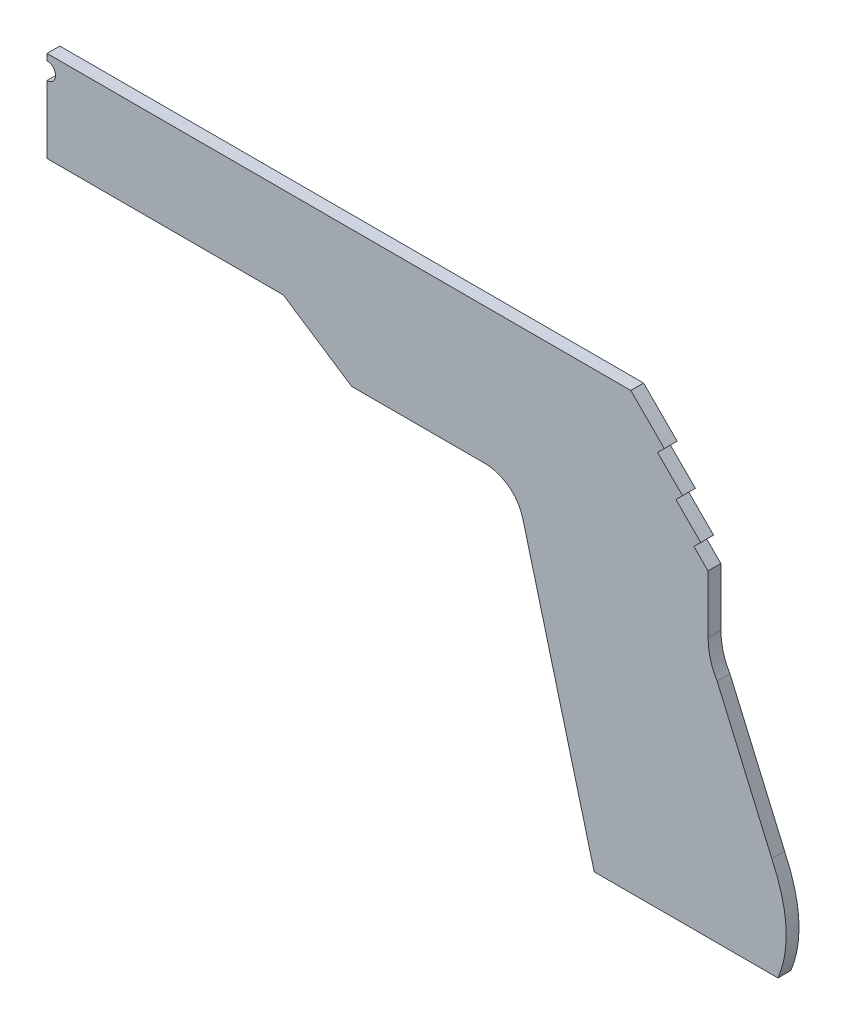
SolidWorks part; units mm, degrees
ref_plane "Front Plane" through (0, 0, 0) normal (0, 0, 1) x (1, 0, 0)
ref_plane "Top Plane" through (0, 0, 0) normal (0, 1, 0) x (1, 0, 0)
ref_plane "Right Plane" through (0, 0, 0) normal (1, 0, 0) x (0, 0, -1)
sketch "Sketch1" plane through (0, 0, 0) normal (0, 0, 1) x (1, 0, 0)
  line L0 (275.2156, 1168.292) -> (1376.0774, 1168.292) construction
  line L2 (544.5582, -97.9207) -> (1910.5582, -97.9207)
  line L3 (1910.5582, -97.9207) -> (1989.0819, -176.4444)
  line L4 (1989.0819, -176.4444) -> (1973.2973, -192.2291)
  line L5 (1973.2973, -192.2291) -> (2031.6653, -250.5972)
  line L6 (2031.6653, -250.5972) -> (2016.2125, -266.05)
  line L7 (2016.2125, -266.05) -> (2074.3189, -324.1564)
  line L8 (2074.3189, -324.1564) -> (2058.3382, -340.1371)
  line L9 (2058.3382, -340.1371) -> (2091.4256, -373.2244)
  line L10 (2091.4256, -373.2244) -> (2091.4256, -508.2244)
  line L11 (2112.4574, -585.6399) -> (2240.5427, -881.6399)
  line L12 (2254.9994, -1116.3328) -> (1824.9994, -1116.3143)
  line L13 (1824.9994, -1116.3143) -> (1658.5751, -486.3143)
  line L14 (1572.5582, -416.3489) -> (1257.5582, -416.3489)
  line L15 (1257.5582, -416.3489) -> (1097.5582, -310.9207)
  line L16 (1097.5582, -310.9207) -> (544.5582, -310.9207)
  line L17 (544.5582, -310.9207) -> (544.5582, -152.9207)
  line L18 (544.5582, -112.9207) -> (544.5582, -97.9207)
  arc A0 (544.5582, -152.9207) -> (544.5582, -112.9207) centre (544.5582, -132.9207) ccw
  spline S0 degree 2 poles (2091.4256, -508.2244) (2091.544, -552.6555) (2113.6236, -587.5127) knots 0 0 0 1 1 1
  spline S1 degree 2 poles (2240.5427, -881.6399) (2299.7604, -1007.5301) (2254.9994, -1116.3328) knots 0 0 0 1 1 1
  spline S2 degree 2 poles (1658.5751, -486.3143) (1649.0454, -450.0834) (1620.6391, -432.151) knots 0 0 0 1 1 1
  spline S3 degree 2 poles (1620.6391, -432.151) (1597.8674, -417.4869) (1572.5582, -416.3489) knots 0 0 0 1 1 1
  dimension "D9" = 20
  dimension "D1" = 430
  dimension "D2" = 1366
  dimension "D3" = 213
  dimension "D4" = 553
  dimension "D5" = 75.2
  dimension "D6" = 630
  dimension "D7" = 315
  dimension "D8" = 160
  dimension "D10" = 15
  dimension "D11" = 158
  dimension "D12" = 296
  dimension "D13" = 113.402
  dimension "D14" = 135
  dimension "D15" = 225
extrude "Boss-Extrude2" add sketch "Sketch1" along normal blind 30 contours S3 S2 L13 L12 S1 L11 S0 L10 L9 L8 L7 L6 L5 L4 L3 L2 L18 A0 L17 L16 L15 L14 region at (1227.5582, -117.9932, 0)
